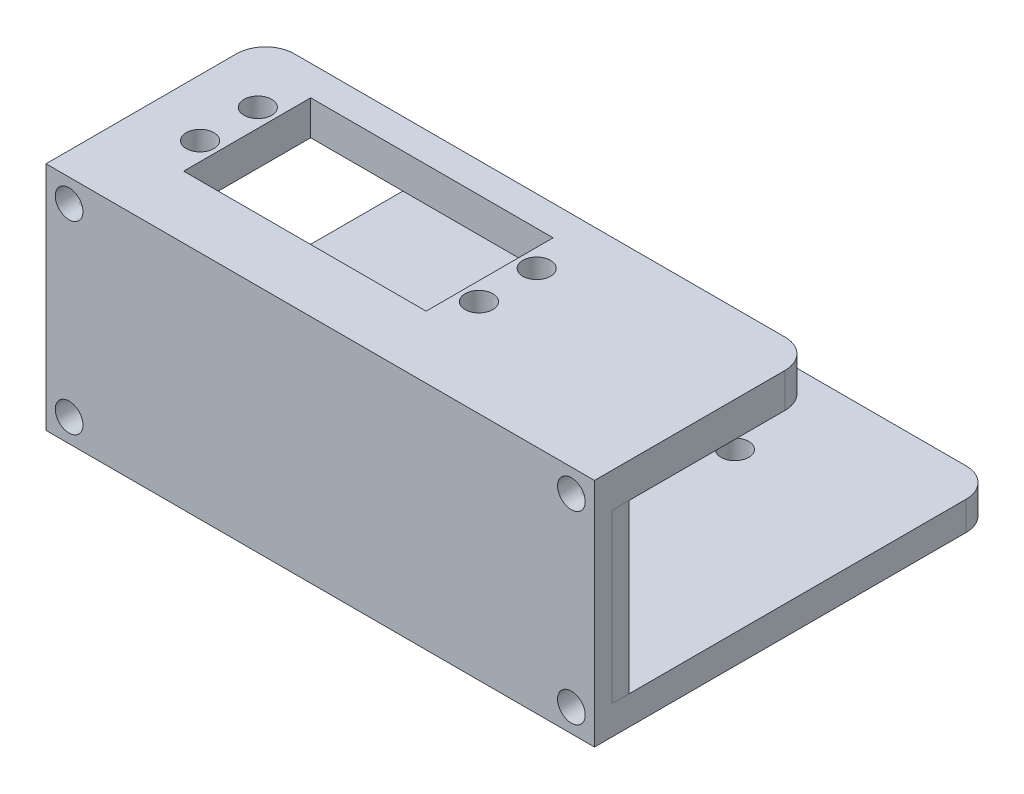
SolidWorks part; units mm, degrees
ref_plane "Front Plane" through (0, 0, 0) normal (0, 0, 1) x (1, 0, 0)
ref_plane "Top Plane" through (0, 0, 0) normal (0, 1, 0) x (1, 0, 0)
ref_plane "Right Plane" through (0, 0, 0) normal (1, 0, 0) x (0, 0, -1)
sketch "Sketch1" plane through (0, 0, 0) normal (0, 1, 0) x (1, 0, 0)
  line L8 (30, -25) -> (30, 20)
  line L9 (-45, 20) -> (30, 20)
  line L10 (-45, -25) -> (30, -25)
  line L11 (-45, 20) -> (-45, -25)
  point P0 (0, 0.6098)
  point P1 (0, 0)
  dimension "D1" = 45
  dimension "D2" = 75
extrude "Boss-Extrude1" add sketch "Sketch1" along normal blind 5
sketch "Sketch2" plane through (0, 5, 0) normal (0, 1, 0) x (1, 0, 0)
  circle A0 centre (-45.1238, -8.5547) radius 2.4
  circle A1 centre (-45.1238, 1.4453) radius 2.4
  circle A2 centre (3.1762, -8.5547) radius 2.4
  circle A3 centre (3.1762, 1.4453) radius 2.4
  dimension "D1" = 4.8
extrude "Cut-Extrude1" [suppressed] cut sketch "Sketch2" against normal blind 5 and the other way through all
sketch "Sketch3" plane through (0, 5, 0) normal (0, 1, 0) x (1, 0, 0)
  line L5 (30, -25) -> (30, 20) construction
  line L6 (-45, 20) -> (30, 20)
  line L7 (-45, 20) -> (-45, 16)
  line L8 (-45, 16) -> (30, 16)
  line L9 (30, 20) -> (30, 16)
  dimension "D1" = 4
extrude "Boss-Extrude3" add sketch "Sketch3" along normal blind 24
sketch "Sketch4" plane through (0, 0, -20) normal (0, 0, -1) x (-1, 0, 0)
  line L0 (45, 29) -> (45, 0) construction
  line L1 (-30, 29) -> (45, 29)
  line L2 (-30, 29) -> (-30, 24)
  line L3 (-30, 24) -> (45, 24)
  line L4 (45, 29) -> (45, 24)
  dimension "D1" = 5
extrude "Boss-Extrude4" add sketch "Sketch4" along normal blind 24
sketch "Sketch6" plane through (0, 29, 0) normal (0, 1, 0) x (1, 0, 0)
  line L5 (-7.5, 26.45) -> (-7.5, 16) construction
  line L6 (-45, 16) -> (30, 16) construction
  line L7 (-27.5, 26.45) -> (12.5, 26.45)
  circle A2 centre (12.5, 26.45) radius 1.6
  circle A3 centre (-27.5, 26.45) radius 1.6
  point P13 (-7.5, 26.45)
  dimension "10" = 10.45
sketch "Sketch9" plane through (0, 29, 0) normal (0, 1, 0) x (1, 0, 0)
  circle A0 centre (-27.5, 26.45) radius 2.4
  circle A1 centre (12.5, 26.45) radius 2.4
  dimension "D1" = 4.8
  dimension "D2" = 4.8
extrude "Cut-Extrude3" cut sketch "Sketch9" against normal through all contours A0 | A1
sketch "Sketch10" plane through (0, 5, 0) normal (0, 1, 0) x (1, 0, 0)
  line L0 (-41.9738, -14.5547) -> (-41.9738, 7.4453)
  line L5 (-40.9738, -13.5547) -> (-0.9738, -13.5547)
  line L6 (-40.9738, -13.5547) -> (-40.9738, 6.4453)
  line L7 (-40.9738, 6.4453) -> (-0.9738, 6.4453)
  line L8 (-0.9738, -13.5547) -> (-0.9738, 6.4453)
  line L9 (-41.9738, 7.4453) -> (0.0262, 7.4453)
  line L10 (0.0262, -14.5547) -> (0.0262, 7.4453)
  line L11 (-41.9738, -14.5547) -> (0.0262, -14.5547)
  dimension "D1" = 1
extrude "Cut-Extrude4" [suppressed] cut sketch "Sketch10" against normal through all contours L0 L9 L10 L11
chamfer "Chamfer1" distance 5 angle 45 1 edges at (-7.5, 5, -16)
chamfer "Chamfer2" distance 5 angle 45 1 edges at (-7.5, 24, -20)
fillet "Fillet1" [suppressed] radius 5
sketch "Sketch13" plane through (0, 5, 0) normal (0, 1, 0) x (1, 0, 0)
  line L1 (-45, 11) -> (30, 11)
  line L2 (-45, 11) -> (-45, -25.3668)
  line L3 (-45, -25.3668) -> (30, -25.3668)
  line L4 (30, 11) -> (30, -25.3668)
  point P5 (-45, 11)
extrude "Boss-Extrude6" add sketch "Sketch13" against normal blind 10 from offset 63 separate body
sketch "Sketch14" plane through (0, 68, 0) normal (0, 1, 0) x (1, 0, 0)
  circle A0 centre (-45.1238, -8.5547) radius 2.4
  circle A9 centre (-45.1238, 1.4453) radius 2.4
  circle A10 centre (3.1762, 1.4453) radius 2.4
  circle A11 centre (3.1762, -8.5547) radius 2.4
extrude "Cut-Extrude5" cut sketch "Sketch14" against normal through all
sketch "Sketch15" plane through (0, 68, 0) normal (0, 1, 0) x (1, 0, 0)
  line L12 (-41.9738, 7.4453) -> (-41.9738, -14.5547)
  line L13 (0.0262, 7.4453) -> (-41.9738, 7.4453)
  line L14 (0.0262, -14.5547) -> (0.0262, 7.4453)
  line L15 (-41.9738, -14.5547) -> (0.0262, -14.5547)
  line L16 (-41.9738, 7.4453) -> (-41.9738, -14.5547)
  line L17 (0.0262, 7.4453) -> (-41.9738, 7.4453)
  line L18 (0.0262, -14.5547) -> (0.0262, 7.4453)
  line L19 (-41.9738, -14.5547) -> (0.0262, -14.5547)
  dimension "D2" = 0
extrude "Cut-Extrude6" cut sketch "Sketch15" against normal through all
sketch "Sketch16" plane through (0, 0, -16) normal (0, 0, 1) x (1, 0, 0)
  line L0 (30, 29) -> (30, 10) construction
  line L1 (-45, 29) -> (30, 29)
  line L2 (-45, 29) -> (-45, 24)
  line L3 (-45, 24) -> (30, 24)
  line L4 (30, 29) -> (30, 24)
  dimension "D1" = 5
extrude "Boss-Extrude7" add sketch "Sketch16" along normal blind 39
sketch "Sketch17" plane through (-45, 0, 0) normal (-1, 0, 0) x (0, 0, 1)
  line L0 (-20, 0) -> (25, 0) construction
  line L1 (-44, 24) -> (25, 24)
  line L2 (-44, 24) -> (-44, 0)
  line L3 (-44, 0) -> (25, 0)
  line L4 (25, 24) -> (25, 0)
extrude "Cut-Extrude7" cut sketch "Sketch17" against normal through all
sketch "Sketch18" plane through (0, 58, 0) normal (0, -1, 0) x (1, 0, 0)
  line L0 (30, 25.3668) -> (30, -11) construction
  line L5 (-45, 25.3668) -> (30, 25.3668)
  line L6 (-45, 25.3668) -> (-45, 22.3668)
  line L7 (-45, 22.3668) -> (30, 22.3668)
  line L8 (30, 25.3668) -> (30, 22.3668)
  dimension "D1" = 3
extrude "Boss-Extrude8" add sketch "Sketch18" along normal blind 34
sketch "Sketch20" plane through (0, 29, 0) normal (0, 1, 0) x (1, 0, 0)
  line L2 (-47.1238, 5.4453) -> (-47.1238, -15.6262)
  line L3 (-47.1238, -15.6262) -> (7.6092, -15.6262)
  line L6 (-17.6474, 9.3738) -> (7.6092, 9.3738)
  line L7 (7.6092, 9.3738) -> (7.6092, -15.6262)
  arc A1 (-17.6474, 9.3738) -> (-47.1238, 5.4453) centre (-32.1238, 5.4453) ccw
  dimension "D1" = 15
  dimension "D2" = 25
extrude "Cut-Extrude8" cut sketch "Sketch20" against normal through all
sketch "Sketch21" plane through (0, 24, 0) normal (0, -1, 0) x (-1, 0, 0)
  circle A0 centre (30.9738, -3.5547) radius 20
extrude "Cut-Extrude9" cut sketch "Sketch21" against normal blind 9
sketch "Sketch22" plane through (0, 29, 0) normal (0, 1, 0) x (1, 0, 0)
  line L0 (30, 37.1801) -> (-7.5, 37.1801)
  line L1 (30, -23) -> (30, 44) construction
sketch "Sketch23" plane through (-45, 0, 0) normal (-1, 0, 0) x (0, 0, 1)
  line L1 (-44, 29) -> (25.3668, 29)
  line L2 (-44, 29) -> (-44, 24)
  line L3 (-44, 24) -> (25.3668, 24)
  line L4 (25.3668, 29) -> (25.3668, 24)
extrude "Boss-Extrude9" add sketch "Sketch23" along normal blind 10
sketch "Sketch24" plane through (-45, 0, 0) normal (-1, 0, 0) x (0, 0, 1)
  line L0 (25.3668, 29) -> (25.3668, 68) construction
  line L1 (-11, 68) -> (25.3668, 68)
  line L2 (-11, 68) -> (-11, 58)
  line L3 (-11, 58) -> (25.3668, 58)
  line L4 (25.3668, 68) -> (25.3668, 58)
extrude "Boss-Extrude10" add sketch "Sketch24" along normal blind 10
sketch "Sketch25" plane through (0, 68, 0) normal (0, 1, 0) x (1, 0, 0)
  circle A1 centre (3.1762, 1.4453) radius 2.4
  circle A2 centre (3.1762, 1.4453) radius 2.4
  circle A3 centre (3.1762, -8.5547) radius 2.4
  circle A4 centre (3.1762, -8.5547) radius 2.4
  circle A5 centre (-45.1238, 1.4453) radius 2.4
  circle A6 centre (-45.1238, 1.4453) radius 2.4
  circle A7 centre (-45.1238, -8.5547) radius 2.4
  circle A8 centre (-45.1238, -8.5547) radius 2.4
  dimension "D1" = 0
  dimension "D2" = 0
  dimension "D3" = 0
  dimension "D4" = 0
extrude "Cut-Extrude10" cut sketch "Sketch25" against normal blind 10
sketch "Sketch26" plane through (0, 24, 0) normal (0, -1, 0) x (1, 0, 0)
  circle A1 centre (-30.9738, 3.5547) radius 20
  circle A2 centre (-30.9738, 3.5547) radius 20
  dimension "D1" = 0
extrude "Cut-Extrude11" cut sketch "Sketch26" against normal blind 10
sketch "Sketch27" plane through (30, 0, 0) normal (1, 0, 0) x (0, 0, -1)
  line L1 (44, 24) -> (-25.3668, 24)
  line L2 (44, 24) -> (44, 29)
  line L3 (44, 29) -> (-25.3668, 29)
  line L4 (-25.3668, 24) -> (-25.3668, 29)
extrude "Boss-Extrude11" add sketch "Sketch27" along normal blind 10
sketch "Sketch28" plane through (-55, 0, 0) normal (-1, 0, 0) x (0, 0, 1)
  line L6 (-11, 68) -> (25.3668, 68)
  line L7 (-11, 68) -> (-11, 64)
  line L9 (25.3668, 68) -> (25.3668, 64)
  line L10 (-11, 64) -> (25.3668, 64)
  dimension "D1" = 4
extrude "Cut-Extrude12" cut sketch "Sketch28" against normal through all
sketch "Sketch29" plane through (0, 0, 25.3668) normal (0, 0, 1) x (1, 0, 0)
  line L5 (-55, 64) -> (40, 64)
  line L6 (-55, 64) -> (-55, 24)
  line L7 (-55, 24) -> (40, 24)
  line L8 (40, 64) -> (40, 24)
extrude "Boss-Extrude13" add sketch "Sketch29" against normal blind 3
sketch "Sketch30" plane through (0, 0, 22.3668) normal (0, 0, -1) x (-1, 0, 0)
  line L1 (-40, 64) -> (-30, 64)
  line L2 (-40, 64) -> (-40, 58)
  line L3 (-40, 58) -> (-30, 58)
  line L4 (-30, 64) -> (-30, 58)
extrude "Boss-Extrude14" add sketch "Sketch30" along normal blind 35
sketch "Sketch31" plane through (0, 0, -11) normal (0, 0, -1) x (-1, 0, 0)
  line L1 (-30, 64) -> (55, 64)
  line L2 (-30, 64) -> (-30, 58)
  line L3 (-30, 58) -> (55, 58)
  line L4 (55, 64) -> (55, 58)
extrude "Boss-Extrude15" add sketch "Sketch31" along normal blind 1.632
sketch "Sketch34" plane through (0, 0, 25.3668) normal (0, 0, 1) x (1, 0, 0)
  line L0 (-51, 60) -> (-51, 28)
  line L1 (-55, 64) -> (40, 64)
  line L2 (-55, 64) -> (-55, 24)
  line L3 (-55, 24) -> (40, 24)
  line L4 (40, 64) -> (40, 24)
  line L5 (-51, 28) -> (36, 28)
  line L6 (36, 60) -> (36, 28)
  line L7 (-51, 60) -> (36, 60)
  circle A0 centre (-51, 60) radius 2.4
  circle A1 centre (36, 60) radius 2.4
  circle A2 centre (-51, 28) radius 2.4
  circle A3 centre (36, 28) radius 2.4
  dimension "D2" = 4.8
  dimension "D3" = 4.8
  dimension "D4" = 4.8
  dimension "D5" = 4.8
  dimension "D1" = 4
extrude "Cut-Extrude13" cut sketch "Sketch34" against normal blind 6 contours A0 | A2 | A3 | A1
sketch "Sketch35" plane through (0, 0, 22.3668) normal (0, 0, -1) x (-1, 0, 0)
  line L1 (-40, 58) -> (55, 58)
  line L2 (-40, 58) -> (-40, 29)
  line L3 (-40, 29) -> (55, 29)
  line L4 (55, 58) -> (55, 29)
extrude "Boss-Extrude18" add sketch "Sketch35" along normal blind 3 separate body
sketch "Sketch37" plane through (0, 24, 0) normal (0, -1, 0) x (1, 0, 0)
  circle A1 centre (-30.9738, 3.5547) radius 20
  circle A2 centre (-30.9738, 3.5547) radius 20
  dimension "D1" = 0
extrude "Cut-Extrude14" cut sketch "Sketch37" against normal up to surface (34 mm away) up to face at (-2.1429, 58, 11.5098)
sketch "Sketch38" plane through (0, 0, 25.3668) normal (0, 0, 1) x (1, 0, 0)
  line L4 (40, 64) -> (-55, 64)
  line L5 (40, 24) -> (40, 64)
  line L6 (-55, 24) -> (40, 24)
  line L7 (-55, 64) -> (-55, 24)
  line L8 (40, 64) -> (-55, 64)
  line L9 (40, 24) -> (40, 64)
  line L10 (-55, 24) -> (40, 24)
  line L11 (-55, 64) -> (-55, 24)
  line L12 (-51, 60) -> (-51, 28)
  line L13 (-51, 28) -> (36, 28)
  line L14 (36, 28) -> (36, 60)
  line L15 (36, 60) -> (-51, 60)
  line L16 (-51, 60) -> (-51, 28)
  line L17 (-51, 28) -> (36, 28)
  line L18 (36, 28) -> (36, 60)
  line L19 (36, 60) -> (-51, 60)
  circle A1 centre (36, 28) radius 2.4
  circle A2 centre (36, 28) radius 2.4
  circle A3 centre (-51, 28) radius 2.4
  circle A4 centre (-51, 28) radius 2.4
  circle A5 centre (36, 60) radius 2.4
  circle A6 centre (36, 60) radius 2.4
  circle A7 centre (-51, 60) radius 2.4
  circle A8 centre (-51, 60) radius 2.4
  dimension "D1" = 0
  dimension "D2" = 0
  dimension "D3" = 0
  dimension "D4" = 0
  dimension "D5" = 0
  dimension "D6" = 0
extrude "Cut-Extrude15" cut sketch "Sketch38" against normal blind 6 contours A8 | A4 | A6 | A2
fillet "Fillet2" radius 5 4 edges at (-55, 61, -12.632) (40, 61, -12.6332) (40, 26.5, -44) (-55, 26.5, -44)
